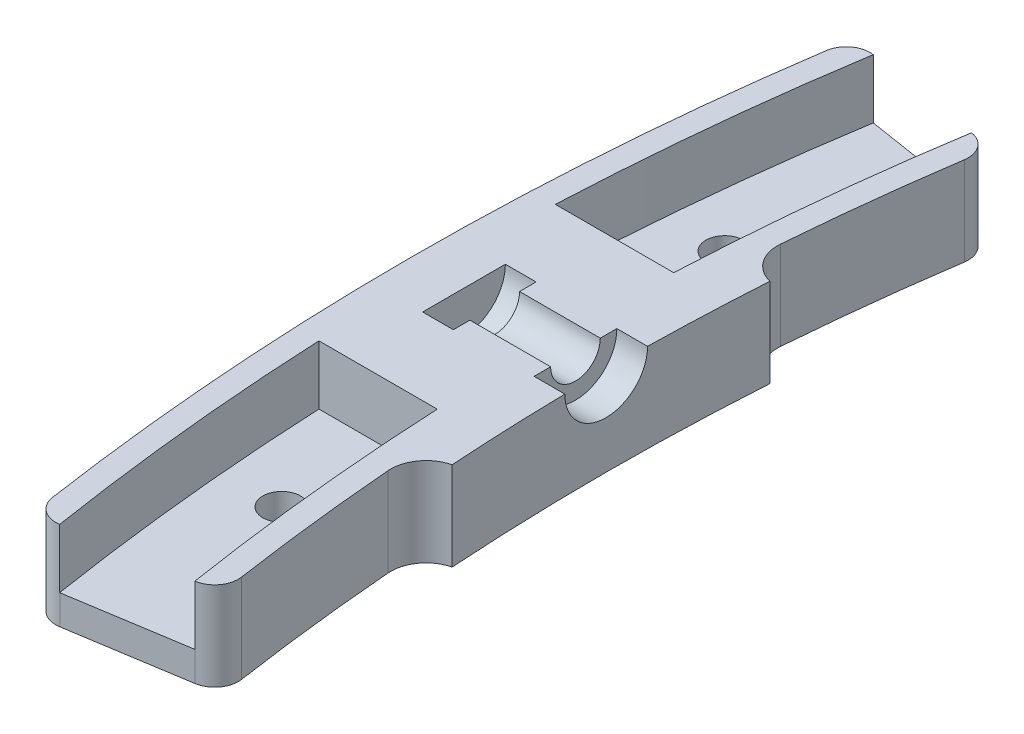
SolidWorks part; units mm, degrees
ref_plane "Front Plane" through (0, 0, 0) normal (0, 0, 1) x (1, 0, 0)
ref_plane "Top Plane" through (0, 0, 0) normal (0, 1, 0) x (1, 0, 0)
ref_plane "Right Plane" through (0, 0, 0) normal (1, 0, 0) x (0, 0, -1)
sketch "Sketch1" plane through (0, 0, 0) normal (0, 1, 0) x (1, 0, 0)
  line L0 (0, 0) -> (-217.2914, -34.4156) construction
  line L1 (0, 0) -> (-217.2914, 34.4156) construction
  line L2 (0, 0) -> (-215, 0) construction
  line L3 (-217.2914, 34.4156) -> (-207.4146, 32.8512)
  line L4 (-207.4146, -32.8512) -> (-217.2914, -34.4156)
  line L5 (0, 0) -> (-219.2668, -34.7285) construction
  line L6 (0, 0) -> (-219.2668, 34.7285) construction
  line L7 (-219.2668, 34.7285) -> (-205.4392, 32.5384)
  line L8 (-219.2668, -34.7285) -> (-205.4392, -32.5384)
  arc A0 (-217.2914, 34.4156) -> (-217.2914, -34.4156) centre (0, 0) ccw
  arc A1 (-207.4146, 32.8512) -> (-207.4146, -32.8512) centre (0, 0) ccw
  arc A2 (-212.353, -33.6334) -> (-212.353, 33.6334) centre (0, 0) cw construction
  arc A4 (-205.4392, 32.5384) -> (-205.4392, -32.5384) centre (0, 0) ccw
  arc A5 (-219.2668, 34.7285) -> (-219.2668, -34.7285) centre (0, 0) ccw
  dimension "D1" = 220
  dimension "D2" = 210
  dimension "D3" = 5
  dimension "D5" = 2
  dimension "D6" = 2
  dimension "D4" = 18
extrude "Boss-Extrude1" add sketch "Sketch1" along normal blind 10 contours A1 L3 A0 L4 | L7 A5 L8 A0 | A4 L7 A1 L8 region at (-220.0938, 0, 0) region at (-214.1555, 0, 0) region at (-208.1432, 0, 0)
ref_plane "Plane1" through (-215, 0, 0) normal (1, 0, 0) x (0, 0, -1)
sketch "Sketch15" plane through (0, 10, 0) normal (0, 1, 0) x (1, 0, 0)
  line L0 (-207.4146, -32.8512) -> (-217.2914, -34.4156) construction
  line L1 (-205, 10) -> (-225, 10)
  line L2 (-205, 10) -> (-205, -10)
  line L3 (-205, -10) -> (-225, -10)
  line L4 (-225, 10) -> (-225, -10)
  line L5 (-205, 10) -> (-225, -10) construction
  line L6 (-205, -10) -> (-225, 10) construction
  line L7 (-217.2914, 34.4156) -> (-207.4146, 32.8512) construction
  line L8 (-207.4146, -32.8512) -> (-217.2914, -34.4156)
  line L9 (-217.2914, 34.4156) -> (-207.4146, 32.8512)
  arc A2 (-207.4146, 32.8512) -> (-207.4146, -32.8512) centre (0, 0) ccw construction
  arc A3 (-217.2914, 34.4156) -> (-217.2914, -34.4156) centre (0, 0) ccw construction
  arc A4 (-207.4146, 32.8512) -> (-207.4146, -32.8512) centre (0, 0) ccw
  arc A5 (-217.2914, 34.4156) -> (-217.2914, -34.4156) centre (0, 0) ccw
  point P0 (-215, 0)
  line M5 (-219.2668, -34.7285) -> (-205.4392, -32.5384)
  line M7 (-205.4392, 32.5384) -> (-219.2668, 34.7285)
  dimension "D1" = 20
  dimension "D2" = 20
extrude "Cut-Extrude1" cut sketch "Sketch15" against normal blind 5 contours A5 L1 A4 M7 | L3 A5 A4 M5 region at (-213.8328, 10, -21.8433) region at (-213.8328, 10, 21.8433)
ref_plane "Plane2" through (-215, 0, 0) normal (-1, 0, 0) x (0, 0, 1)
sketch "Sketch12" plane through (0, 0, 0) normal (0, 1, 0) x (1, 0, 0)
  line L0 (0, 0) -> (-214.1819, -18.7385) construction
  line L1 (0, 0) -> (-213.1606, -28.0631) construction
  line L2 (0, 0) -> (-215, 0) construction
  line L3 (0, 0) -> (-215, 0) construction
  line L4 (0, 0) -> (-214.1819, 18.7385) construction
  line L5 (0, 0) -> (-213.1606, 28.0631) construction
  arc A0 (-212.353, 33.6334) -> (-212.353, -33.6334) centre (0, 0) ccw construction
  dimension "D1" = 10
  dimension "D2" = 15
hole_wizard "Ø3.2 (3.2) Diameter Hole1" positions "Sketch18" profile "Sketch17" hole size "Ø3.2" standard "ISO" end condition through all
sketch "Sketch18" plane through (0, 0, 0) normal (0, -1, 0) x (-1, 0, 0)
  point P3 (214.1819, -18.7385)
  point P6 (214.1819, 18.7385)
  point P13 (0, 0)
  point P14 (0, 0)
sketch "Sketch17" plane through (-214.1819, 0, 18.7385) normal (1, 0, 0) x (0, 0, -1)
  line L0 (0, 0) -> (0, 10)
  line L1 (0, 10) -> (1.6, 10)
  line L2 (1.6, 10) -> (1.6, 0)
  line L5 (1.6, 0) -> (0, 0)
  line L11 (0, -6.35) -> (0, 107.95) construction
  dimension "Thru Hole Dia." = 3.2
  dimension "Thru Hole Depth" = 10
sketch "Sketch19" plane through (0, 0, 0) normal (0, 1, 0) x (1, 0, 0)
  line L0 (0, 0) -> (-205.06, -13.4403) construction
  line L1 (0, 0) -> (-205.5, 0) construction
  line L2 (-205.06, -13.4403) -> (-207.5547, -13.6039)
  line L3 (-205.06, 13.4403) -> (-207.5547, 13.6039)
  arc A0 (-205.06, 13.4403) -> (-205.06, -13.4403) centre (0, 0) ccw
  arc A1 (-205.4392, 32.5384) -> (-205.4392, -32.5384) centre (0, 0) ccw construction
  arc A2 (-207.5547, 13.6039) -> (-207.5547, -13.6039) centre (0, 0) ccw
  dimension "D1" = 205.5
  dimension "D2" = 3.75
extrude "Boss-Extrude2" add sketch "Sketch19" along normal blind 10
fillet "Fillet1" radius 3 2 edges at (-207.5547, 5, -13.6039) (-207.5547, 5, 13.6039)
fillet "Fillet2" radius 2 4 edges at (-219.2668, 5, -34.7285) (-219.2668, 5, 34.7285) (-205.4392, 5, 32.5384) (-205.4392, 5, -32.5384)
sketch "Sketch20" plane through (0, 10, 0) normal (0, 1, 0) x (1, 0, 0)
  line L0 (0, 0) -> (-185, 0) construction
  line L1 (-185, 0) -> (-197.5, 0) construction
  dimension "D1" = 185
  dimension "D2" = 12.5
ref_plane "Plane3" through (-197.5, 0, 0) normal (1, 0, 0) x (0, 0, -1)
sketch "Sketch26" plane through (0, 0, 0) normal (0, -1, 0) x (1, 0, 0)
  line L2 (-217.2825, -34.4142) -> (-207.4051, -32.8497)
  line L3 (-207.4051, 32.8497) -> (-217.2825, 34.4142)
  line L4 (-217.2825, -34.4142) -> (-207.4051, -32.8497)
  line L5 (-207.4051, 32.8497) -> (-217.2825, 34.4142)
  arc A10 (-219.5735, 32.7337) -> (-219.5735, -32.7337) centre (0, 0) ccw
  arc A11 (-219.5735, -32.7337) -> (-217.2825, -34.4142) centre (-217.5953, -32.4388) ccw
  arc A12 (-207.4051, -32.8497) -> (-205.7397, -30.5803) centre (-207.718, -30.8744) ccw
  arc A13 (-207.337, -16.5936) -> (-205.7397, -30.5803) centre (0, 0) ccw
  arc A14 (-205.06, -13.4403) -> (-207.337, -16.5936) centre (-204.3466, -16.3543) ccw
  arc A15 (-205.06, 13.4403) -> (-205.06, -13.4403) centre (0, 0) ccw
  arc A16 (-207.337, 16.5936) -> (-205.06, 13.4403) centre (-204.3466, 16.3543) ccw
  arc A17 (-205.7397, 30.5803) -> (-207.337, 16.5936) centre (0, 0) ccw
  arc A18 (-205.7397, 30.5803) -> (-207.4051, 32.8497) centre (-207.718, 30.8744) ccw
  arc A19 (-217.2825, 34.4142) -> (-219.5735, 32.7337) centre (-217.5953, 32.4388) ccw
  arc A20 (-219.5735, 32.7337) -> (-219.5735, -32.7337) centre (0, 0) ccw
  arc A21 (-219.5735, -32.7337) -> (-217.2825, -34.4142) centre (-217.5953, -32.4388) ccw
  arc A22 (-207.4051, -32.8497) -> (-205.7397, -30.5803) centre (-207.718, -30.8744) ccw
  arc A23 (-207.337, -16.5936) -> (-205.7397, -30.5803) centre (0, 0) ccw
  arc A24 (-205.06, -13.4403) -> (-207.337, -16.5936) centre (-204.3466, -16.3543) ccw
  arc A25 (-205.06, 13.4403) -> (-205.06, -13.4403) centre (0, 0) ccw
  arc A26 (-207.337, 16.5936) -> (-205.06, 13.4403) centre (-204.3466, 16.3543) ccw
  arc A27 (-205.7397, 30.5803) -> (-207.337, 16.5936) centre (0, 0) ccw
  arc A28 (-205.7397, 30.5803) -> (-207.4051, 32.8497) centre (-207.718, 30.8744) ccw
  arc A29 (-217.2825, 34.4142) -> (-219.5735, 32.7337) centre (-217.5953, 32.4388) ccw
  dimension "D1" = 0
extrude "Cut-Extrude6" cut sketch "Sketch26" against normal blind 2.5
sketch "Sketch27" plane through (0, 0, 0) normal (0, 1, 0) x (1, 0, 0)
  line L0 (0, 0) -> (-205, 0) construction
  line L1 (0, 0) -> (-215, 0) construction
  line L2 (-205, 0) -> (-217.5, 0) construction
  arc A0 (-205.06, 13.4403) -> (-205.06, -13.4403) centre (0, 0) ccw construction
  point P5 (-205.5, 0)
  dimension "D1" = 205
  dimension "D2" = 12.5
ref_plane "Plane4" through (-217.5, 0, 0) normal (1, 0, 0) x (0, 0, -1)
sketch "Sketch28" plane through (-217.5, 0, 0) normal (1, 0, 0) x (0, 0, -1)
  line L0 (13.4403, 10) -> (-13.4403, 10) construction
  circle A0 centre (0, 10) radius 3.5
  dimension "D1" = 7
extrude "Cut-Extrude7" cut sketch "Sketch28" along normal blind 2.6
sketch "Sketch29" plane through (0, 10, 0) normal (0, 1, 0) x (1, 0, 0)
  line L0 (-205, 0) -> (-217.5, 0) construction
  line L1 (-208.0702, 0) -> (-205.4702, 0)
  line L2 (-208.0702, 0) -> (-208.0702, -3.5)
  line L3 (-208.0702, -3.5) -> (-205.4702, -3.5)
  line L4 (-205.4702, 0) -> (-205.4702, -3.5)
  line L6 (-217.5, 0) -> (-205, 0) construction
  arc A0 (-205.06, 13.4403) -> (-205.06, -13.4403) centre (0, 0) ccw construction
  dimension "D1" = 2.6
  dimension "D2" = 7
revolve "Cut-Revolve1" cut sketch "Sketch29" angle 360 about L6
sketch "Sketch30" plane through (-208.0702, 0, 0) normal (1, 0, 0) x (0, 0, -1)
  line L0 (3.5, 10) -> (-3.5, 10) construction
  circle A0 centre (0, 10) radius 2.1
  dimension "D1" = 4.2
extrude "Cut-Extrude8" cut sketch "Sketch30" against normal up to surface (6.8298 mm away) up to face at (-214.9, 8.25, 0)
